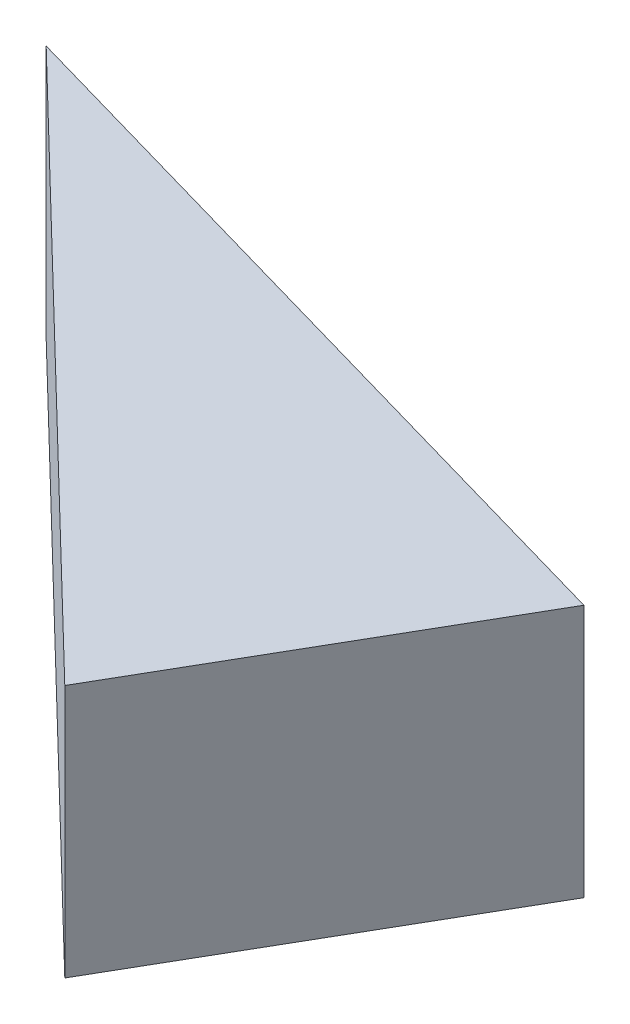
SolidWorks part; units mm, degrees
ref_plane "Front Plane" through (0, 0, 0) normal (0, 0, 1) x (1, 0, 0)
ref_plane "Top Plane" through (0, 0, 0) normal (0, 1, 0) x (1, 0, 0)
ref_plane "Right Plane" through (0, 0, 0) normal (1, 0, 0) x (0, 0, -1)
sketch "Sketch1" plane through (0, 0, 0) normal (0, 1, 0) x (1, 0, 0)
  line L0 (19.05, -10.9985) -> (-44.3859, 25.6262) construction
  line L1 (0, -43.9941) -> (38.1, 21.997)
  line L4 (38.1, 21.997) -> (-112.9323, 65.2015)
  line L5 (-112.9323, 65.2015) -> (0, -43.9941)
  line L6 (-112.9323, 65.2015) -> (19.05, -10.9985)
  dimension "D1" = 76.2
  dimension "D2" = 152.4
extrude "Boss-Extrude1" add sketch "Sketch1" along normal blind 50.8 contours L6 L5 L1 | L4 L6 L1 region at (-31.2941, 0, -3.403) region at (-18.5941, 0, -25.4)
